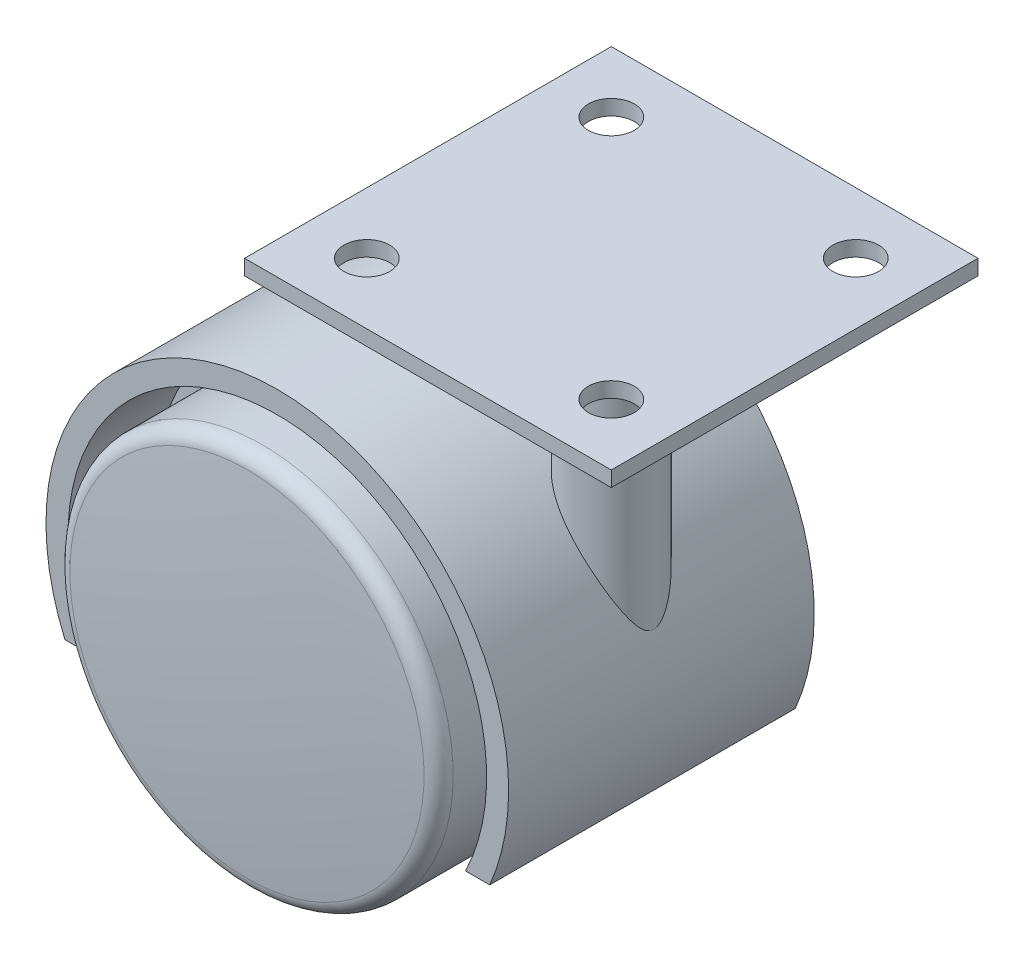
SolidWorks part; units mm, degrees
ref_plane "Front Plane" through (0, 0, 0) normal (0, 0, 1) x (1, 0, 0)
ref_plane "Top Plane" through (0, 0, 0) normal (0, 1, 0) x (1, 0, 0)
ref_plane "Right Plane" through (0, 0, 0) normal (1, 0, 0) x (0, 0, -1)
sketch "Sketch1" plane through (0, 0, 0) normal (0, 0, 1) x (1, 0, 0)
  line L0 (0, -19.8438) -> (18.8277, -19.8438) construction
  line L1 (18.8277, -19.8438) -> (18.8277, 37.3062) construction
  line L2 (23.241, 37.3062) -> (14.4145, 37.3062) construction
  line L4 (14.4145, 37.3062) -> (14.4145, 19.2326) construction
  line L5 (23.241, 37.3062) -> (23.241, -6.1258) construction
  line L6 (-22.0668, -9.525) -> (22.0668, -9.525) construction
  line L7 (0, 19.8438) -> (0, 21.7488) construction
  line L8 (-0.2223, 37.3062) -> (37.8777, 37.3062)
  line L9 (-0.2223, 37.3062) -> (-0.2223, 35.7188)
  line L10 (-0.2223, 35.7188) -> (37.8777, 35.7188)
  line L11 (37.8777, 37.3062) -> (37.8777, 35.7188)
  circle A0 centre (0, 0) radius 19.8438
  arc A1 (19.552, -9.525) -> (-19.552, -9.525) centre (0, 0) ccw construction
  arc A2 (22.0668, -9.525) -> (-22.0668, -9.525) centre (0, 0) ccw construction
  circle A4 centre (0, 0) radius 24.0348 construction
  circle A5 centre (0, 0) radius 21.7488 construction
  point P10 (18.8277, 37.3062)
  point P14 (27.305, 0)
  point P16 (29.591, 0)
  dimension "Wheel Dia" = 39.6875
  dimension "Mount Height" = 57.15
  dimension "D9" = 9.525
  dimension "Plate Thickness" = 1.5875
  dimension "Plate Length" = 38.1
  dimension "D1" = 1.905
  dimension "D2" = 42.8625
  dimension "D7" = 2.286
sketch "Sketch16" plane through (0, 0, 0) normal (0, 0, 1) x (1, 0, 0)
  line L1 (-0.2223, 37.3062) -> (37.8777, 37.3062)
  line L2 (-0.2223, 37.3062) -> (-0.2223, 35.7188)
  line L3 (-0.2223, 35.7188) -> (37.8777, 35.7188)
  line L4 (37.8777, 37.3062) -> (37.8777, 35.7188)
extrude "Boss-Extrude1" add sketch "Sketch16" along normal mid plane 38.1
sketch "Sketch17" plane through (0, 37.3062, 0) normal (0, 1, 0) x (1, 0, 0)
  line L0 (-0.2223, 19.05) -> (37.8777, -19.05) construction
  line L1 (18.8277, 0) -> (18.8277, 19.05) construction
  line L2 (18.8277, 0) -> (37.8777, 0) construction
  line L3 (-0.2223, 0) -> (37.8777, 0) construction
  line L4 (37.8777, -19.05) -> (37.8777, 19.05) construction
  line L5 (37.8777, 19.05) -> (-0.2223, 19.05) construction
  circle A0 centre (-1.016, 10.3187) radius 2.3812
  circle A1 centre (38.6715, 10.3187) radius 2.3812
  circle A2 centre (38.6715, -10.3187) radius 2.3812
  circle A3 centre (-1.016, -10.3187) radius 2.3812
  dimension "D1" = 4.7625
  dimension "D2" = 39.6875
  dimension "D3" = 20.6375
extrude "Plate 1 holes" [suppressed] cut sketch "Sketch17" against normal through all
sketch "Sketch18" plane through (0, 37.3062, 0) normal (0, 1, 0) x (1, 0, 0)
  line L0 (-0.2223, 19.05) -> (37.8777, -19.05) construction
  line L1 (18.8277, 0) -> (18.8277, 19.05) construction
  line L2 (18.8277, 0) -> (37.8777, 0) construction
  line L3 (37.8777, -19.05) -> (37.8777, 19.05) construction
  line L4 (37.8777, 19.05) -> (-0.2223, 19.05) construction
  circle A0 centre (6.1277, 12.7) radius 2.3813
  circle A1 centre (31.5277, 12.7) radius 2.3812
  circle A2 centre (31.5277, -12.7) radius 2.3812
  circle A3 centre (6.1277, -12.7) radius 2.3813
  dimension "D3" = 4.7625
  dimension "D1" = 25.4
  dimension "D2" = 25.4
extrude "Plate 2 holes" cut sketch "Sketch18" against normal through all
sketch "Sketch2" plane through (0, 0, 0) normal (1, 0, 0) x (0, 0, -1)
  line L0 (-19.8438, 0) -> (19.8438, 0) construction
  line L1 (-9.271, 4.7625) -> (-9.271, 19.8438)
  line L2 (-9.271, 19.8438) -> (-17.4441, 19.8438)
  line L3 (-19.8438, 0) -> (-19.8438, 19.8438) construction
  line L4 (-19.8438, 0) -> (0, 0)
  line L5 (0, 0) -> (0, 20.8454) construction
  line L6 (0, 21.7488) -> (0, -9.525) construction
  line L7 (19.8438, 0) -> (0, 0)
  line L8 (9.271, 19.8438) -> (17.4441, 19.8438)
  line L9 (9.271, 4.7625) -> (9.271, 19.8438)
  line L10 (-9.271, 4.7625) -> (9.271, 4.7625)
  line L11 (0, 0) -> (0, 4.7625) construction
  arc A0 (-19.0253, 18.3972) -> (-19.8438, 0) centre (187.3382, 0) ccw
  arc A1 (19.0253, 18.3972) -> (19.8438, 0) centre (-187.3382, 0) cw
  arc A2 (-17.4441, 19.8438) -> (-19.0253, 18.3972) centre (-17.4441, 18.2563) ccw
  arc A3 (19.0253, 18.3972) -> (17.4441, 19.8438) centre (17.4441, 18.2563) ccw
  point P19 (-18.8912, 19.8438)
  point P22 (18.8912, 19.8438)
  dimension "D6" = 1.5875
  dimension "Width" = 39.6875
  dimension "D2" = 39.6875
  dimension "D3" = 9.271
  dimension "D5" = 0.9525
  dimension "D4" = 4.7625
revolve "Revolve1" add sketch "Sketch2" angle 360 about L0
sketch "Sketch5" plane through (0, 0, 0) normal (0, 0, 1) x (1, 0, 0)
  line L0 (-22.0668, -9.525) -> (22.0668, -9.525) construction
  line L1 (-22.0668, -9.525) -> (-19.552, -9.525)
  line L2 (19.552, -9.525) -> (22.0668, -9.525)
  arc A0 (22.0668, -9.525) -> (-22.0668, -9.525) centre (0, 0) ccw construction
  arc A1 (19.552, -9.525) -> (-19.552, -9.525) centre (0, 0) ccw construction
  arc A2 (22.0668, -9.525) -> (-22.0668, -9.525) centre (0, 0) ccw
  arc A3 (19.552, -9.525) -> (-19.552, -9.525) centre (0, 0) ccw
extrude "Extrude1" add sketch "Sketch5" along normal mid plane 31.75 separate body
sketch "Sketch7" plane through (0, 0, 0) normal (0, 0, 1) x (1, 0, 0)
  line L0 (18.8277, 35.7188) -> (18.8278, 0)
  line L1 (18.8277, -19.8438) -> (18.8277, 37.3062) construction
  line L2 (-0.2223, 35.7188) -> (37.8777, 35.7188) construction
  line L3 (22.8917, 24.0347) -> (22.8917, 28.8353)
  line L4 (22.8917, 24.0347) -> (23.241, 24.0347)
  line L5 (23.241, 37.3062) -> (23.241, -6.1258) construction
  line L6 (23.241, 24.0347) -> (23.241, 0)
  line L7 (23.241, 0) -> (18.8278, 0)
  line L10 (22.8917, 28.8353) -> (23.9331, 28.8353)
  line L11 (23.9331, 32.7978) -> (30.5117, 35.7188)
  line L12 (18.8277, 35.7188) -> (30.5117, 35.7188)
  line L13 (18.8277, 35.7188) -> (18.8277, 37.3062) construction
  arc A0 (23.9331, 28.8353) -> (23.9331, 32.7978) centre (19.4711, 30.8165) ccw
  arc A1 (22.0668, -9.525) -> (-22.0668, -9.525) centre (0, 0) ccw construction
  dimension "D1" = 8.128
  dimension "D2" = 2.921
  dimension "D3" = 3.9624
  dimension "D5" = 1.0414
  dimension "D6" = 23.368
revolve "Revolve3" add sketch "Sketch7" angle 360 about L1
sketch "Sketch15" plane through (0, 0, 15.875) normal (0, 0, 1) x (1, 0, 0)
  arc A0 (19.552, -9.525) -> (-19.552, -9.525) centre (0, 0) ccw construction
  arc A1 (19.552, -9.525) -> (-19.552, -9.525) centre (0, 0) ccw
extrude "Extrude7" cut sketch "Sketch15" against normal through all and the other way through all
sketch "Sketch8" plane through (0, 0, 0) normal (0, 0, 1) x (1, 0, 0)
  line L0 (-22.0668, -9.525) -> (22.0668, -9.525) construction
  line L1 (-19.552, -9.525) -> (19.552, -9.525)
  arc A0 (19.552, -9.525) -> (-19.552, -9.525) centre (0, 0) ccw construction
  arc A1 (19.552, -9.525) -> (-19.552, -9.525) centre (0, 0) ccw
extrude "Extrude2" add sketch "Sketch8" along normal offset from surface 2.54 and the other way offset from surface 2.54 up to face at (0, -19.8438, 9.271) other way up to face at (0, -4.7625, -9.271)
combine bodies "Combine1" operation type add bodies to combine 107 105 102
sketch "Sketch11" [suppressed] plane through (0, 0, 0) normal (0, 0, 1) x (1, 0, 0)
  line L0 (-27.7643, 7.1501) -> (-49.2222, 7.1501)
  line L1 (-49.2222, 7.1501) -> (-49.2222, 11.9126)
  line L2 (-49.2222, 11.9126) -> (-31.485, 16.6653)
  line L3 (-33.5727, 11.9126) -> (-26.0782, 11.9126)
  circle A2 centre (0, 0) radius 28.6702 construction
  arc A3 (34.2268, -9.8771) -> (-34.2268, -9.8771) centre (0, 0) ccw
  arc A4 (-31.485, 16.6653) -> (-33.5727, 11.9126) centre (0, 0) ccw
  arc A5 (-26.0782, 11.9126) -> (-27.7643, 7.1501) centre (0, 0) ccw
  arc A6 (33.0066, -9.525) -> (-33.0066, -9.525) centre (0, 0) ccw construction
  point P3 (-33.6012, 7.1501)
  dimension "D5" = 15
  dimension "D1" = 1.27
  dimension "D2" = 7.1501
  dimension "D3" = 4.7625
  dimension "D4" = 15.621
extrude "Extrude3" [suppressed] add sketch "Sketch11" along normal mid plane 28.575 separate body
sketch "Sketch12" [suppressed] plane through (0, 0, 14.2875) normal (0, 0, 1) x (1, 0, 0)
  line L8 (-26.0782, 11.9126) -> (-33.5727, 11.9126)
  line L9 (-31.485, 16.6653) -> (-49.2222, 11.9126)
  line L10 (-49.2222, 11.9126) -> (-49.2222, 7.1501)
  line L11 (-49.2222, 7.1501) -> (-27.7643, 7.1501)
  line L12 (-26.0782, 11.9126) -> (-33.5727, 11.9126)
  line L15 (-34.8986, 7.1501) -> (-27.7643, 7.1501)
  arc A4 (-26.0782, 11.9126) -> (-27.7643, 7.1501) centre (0, 0) ccw
  arc A13 (-31.485, 16.6653) -> (-33.5727, 11.9126) centre (0, 0) ccw
  arc A14 (-26.0782, 11.9126) -> (-27.7643, 7.1501) centre (0, 0) ccw
  arc A15 (-33.5727, 11.9126) -> (-34.8986, 7.1501) centre (0, 0) ccw
  dimension "D1" = 0
extrude "Extrude4" [suppressed] cut sketch "Sketch12" against normal offset from surface (10.3251 mm away) 3.9624
sketch "Sketch13" [suppressed] plane through (0, 0, -14.2875) normal (0, 0, -1) x (-1, 0, 0)
  line L2 (27.7643, 7.1501) -> (34.8986, 7.1501)
  line L3 (27.7643, 7.1501) -> (34.8986, 7.1501)
  line L4 (33.5727, 11.9126) -> (26.0782, 11.9126)
  line L5 (33.5727, 11.9126) -> (26.0782, 11.9126)
  arc A2 (27.7643, 7.1501) -> (26.0782, 11.9126) centre (0, 0) ccw
  arc A3 (27.7643, 7.1501) -> (26.0782, 11.9126) centre (0, 0) ccw
  arc A4 (34.8986, 7.1501) -> (33.5727, 11.9126) centre (0, 0) ccw
  arc A5 (34.8986, 7.1501) -> (33.5727, 11.9126) centre (0, 0) ccw
  dimension "D1" = 0
extrude "Extrude5" [suppressed] cut sketch "Sketch13" against normal offset from surface (10.4775 mm away) 3.81
sketch "Sketch14" [suppressed] plane through (0, 0, 0) normal (0, 0, 1) x (1, 0, 0)
  line L0 (-31.5803, 5.5685) -> (-33.8316, 5.9654)
  line L1 (-20.6126, 24.5651) -> (-22.082, 26.3163)
  line L2 (0, 0) -> (-42.5121, 0) construction
  arc A0 (30.6202, -9.525) -> (-30.6202, -9.525) centre (0, 0) ccw construction
  arc A1 (33.0066, -9.525) -> (-33.0066, -9.525) centre (0, 0) ccw construction
  arc A2 (-20.6126, 24.5651) -> (-31.5803, 5.5685) centre (0, 0) ccw
  arc A3 (-22.082, 26.3163) -> (-33.8316, 5.9654) centre (0, 0) ccw
  dimension "D1" = 10
  dimension "D2" = 50
extrude "Extrude8" [suppressed] cut sketch "Sketch14" against normal mid plane 7.9375
equation "\"D5@Sketch2\" = \"D4@Sketch2\"/5"
equation "\"D1@Extrude1\" = \"Width@Sketch2\"*.80"
equation "\"D2@Sketch2\" = \"Wheel Dia@Sketch1\""
